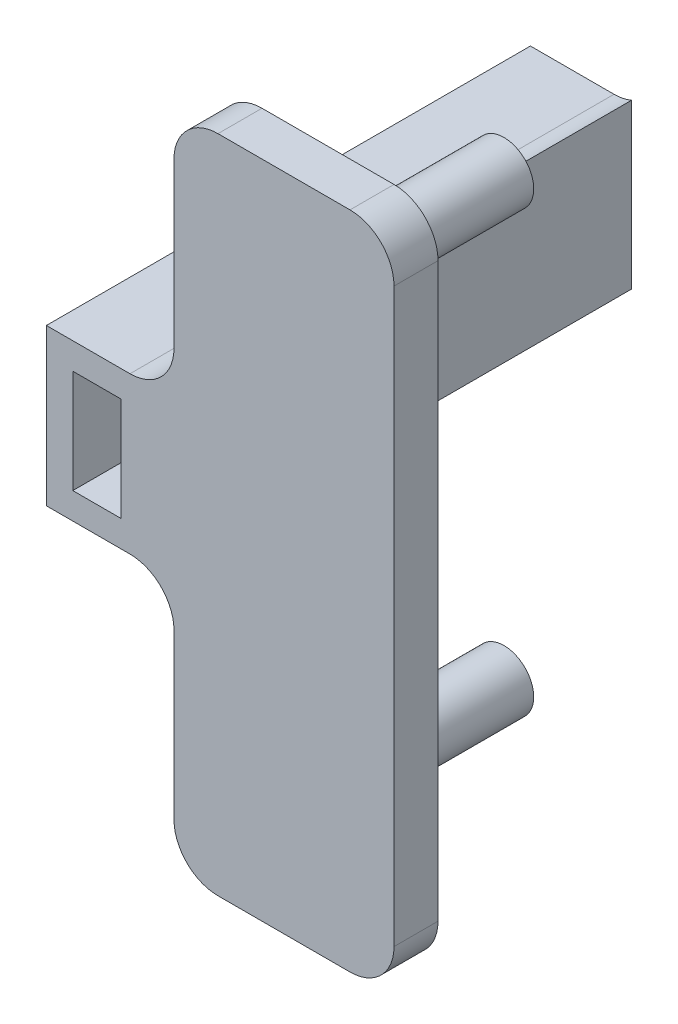
SolidWorks part; units mm, degrees
ref_plane "Front Plane" through (0, 0, 0) normal (0, 0, 1) x (1, 0, 0)
ref_plane "Top Plane" through (0, 0, 0) normal (0, 1, 0) x (1, 0, 0)
ref_plane "Right Plane" through (0, 0, 0) normal (1, 0, 0) x (0, 0, -1)
sketch "Sketch1" plane through (0, 0, 0) normal (0, 0, 1) x (1, 0, 0)
  line L0 (44, 65) -> (44, 45) construction
  line L1 (44, 55) -> (35.5, 55) construction
  line L2 (49, 70) -> (39, 70)
  line L3 (49, 70) -> (49, 40)
  line L4 (49, 40) -> (39, 40)
  line L5 (39, 70) -> (39, 58.55)
  line L6 (37.8, 58.55) -> (37.8, 51.45) construction
  line L7 (36.6, 57.35) -> (34.4, 57.35)
  line L8 (36.6, 57.35) -> (36.6, 52.65)
  line L9 (36.6, 52.65) -> (34.4, 52.65)
  line L10 (34.4, 57.35) -> (34.4, 52.65)
  line L11 (36.6, 57.35) -> (34.4, 52.65) construction
  line L12 (36.6, 52.65) -> (34.4, 57.35) construction
  line L13 (37.8, 51.45) -> (33.2, 51.45) construction
  line L14 (33.2, 58.55) -> (33.2, 51.45) construction
  line L15 (37.8, 58.55) -> (33.2, 58.55) construction
  line L16 (33.2, 58.55) -> (39, 58.55)
  line L17 (33.2, 51.45) -> (39, 51.45)
  line L18 (33.2, 58.55) -> (33.2, 51.45)
  line L19 (39, 51.45) -> (39, 40)
  circle A0 centre (44, 45) radius 1.65 construction
  circle A1 centre (44, 65) radius 1.65 construction
  circle A2 centre (44, 45) radius 1.65 construction
  circle A3 centre (44, 65) radius 1.65 construction
  dimension "D1" = 5
  dimension "D2" = 4.7
  dimension "D3" = 2.2
  dimension "D4" = 8.5
  dimension "D6" = 5
  dimension "D7" = 5
  dimension "D8" = 5
  dimension "D5" = 1.2
extrude "Boss-Extrude1" add sketch "Sketch1" along normal blind 2
sketch "Sketch2" plane through (0, 0, 0) normal (0, 0, -1) x (-1, 0, 0)
  line L0 (-36.6, 57.35) -> (-34.4, 57.35) construction
  line L1 (-34.4, 57.35) -> (-34.4, 52.65) construction
  line L2 (-34.4, 52.65) -> (-36.6, 52.65) construction
  line L3 (-36.6, 52.65) -> (-36.6, 57.35) construction
  line L4 (-36.6, 57.35) -> (-34.4, 57.35)
  line L5 (-34.4, 57.35) -> (-34.4, 52.65)
  line L6 (-34.4, 52.65) -> (-36.6, 52.65)
  line L7 (-36.6, 52.65) -> (-36.6, 57.35)
  line L8 (-39, 58.55) -> (-33.2, 58.55) construction
  line L9 (-33.2, 51.45) -> (-37.8, 51.45)
  line L10 (-33.2, 51.45) -> (-33.2, 58.55)
  line L11 (-33.2, 58.55) -> (-37.8, 58.55)
  line L12 (-37.8, 51.45) -> (-37.8, 58.55)
  dimension "D1" = 1.2
extrude "Boss-Extrude2" add sketch "Sketch2" along normal blind 20
sketch "Sketch3" plane through (0, 0, -20) normal (0, 0, -1) x (-1, 0, 0)
  line L0 (-34.4, 57.35) -> (-36.6, 57.35) construction
  line L1 (-34.4, 52.65) -> (-34.4, 57.35) construction
  line L2 (-36.6, 52.65) -> (-34.4, 52.65) construction
  line L3 (-36.6, 57.35) -> (-36.6, 52.65) construction
  line L4 (-34.4, 57.35) -> (-36.6, 57.35)
  line L5 (-34.4, 52.65) -> (-34.4, 57.35)
  line L6 (-36.6, 52.65) -> (-34.4, 52.65)
  line L7 (-36.6, 57.35) -> (-36.6, 52.65)
extrude "Boss-Extrude3" add sketch "Sketch3" against normal blind 1
sketch "Sketch5" plane through (0, 0, 0) normal (0, 0, -1) x (-1, 0, 0)
  circle A0 centre (-44, 45) radius 1.65 construction
  circle A1 centre (-44, 65) radius 1.65 construction
  circle A9 centre (-44, 65) radius 1.65 construction
  circle A10 centre (-44, 45) radius 1.65 construction
  circle A11 centre (-44, 45) radius 1.35
  circle A12 centre (-44, 65) radius 1.35
  dimension "D1" = 0.3
extrude "Boss-Extrude4" add sketch "Sketch5" along normal blind 8
fillet "Fillet1" radius 2 6 edges at (49, 70, 1) (49, 40, 1) (39, 40, 1) (39, 70, 1) (39, 58.55, 1) (39, 51.45, 1)
sketch "Sketch6" plane through (0, 0, 0) normal (0, 0, -1) x (-1, 0, 0)
  line L0 (-40, 31.1203) -> (-40, 78.8797) construction
  line L1 (-40, 31.1203) -> (-40, 78.8797) construction
  line L2 (-39.7, 31.1203) -> (-39.7, 78.8797) construction
  line L3 (-37.8, 58.717) -> (-37.8, 51.283) construction
  line L4 (-37.8, 58.717) -> (-37.8, 51.283)
  line L5 (-37.8, 51.283) -> (-39.7, 51.283)
  line L6 (-39.7, 51.283) -> (-39.7, 58.717)
  line L7 (-39.7, 58.717) -> (-37.8, 58.717)
  dimension "D1" = 0.3
extrude "Boss-Extrude5" add sketch "Sketch6" along normal blind 8
